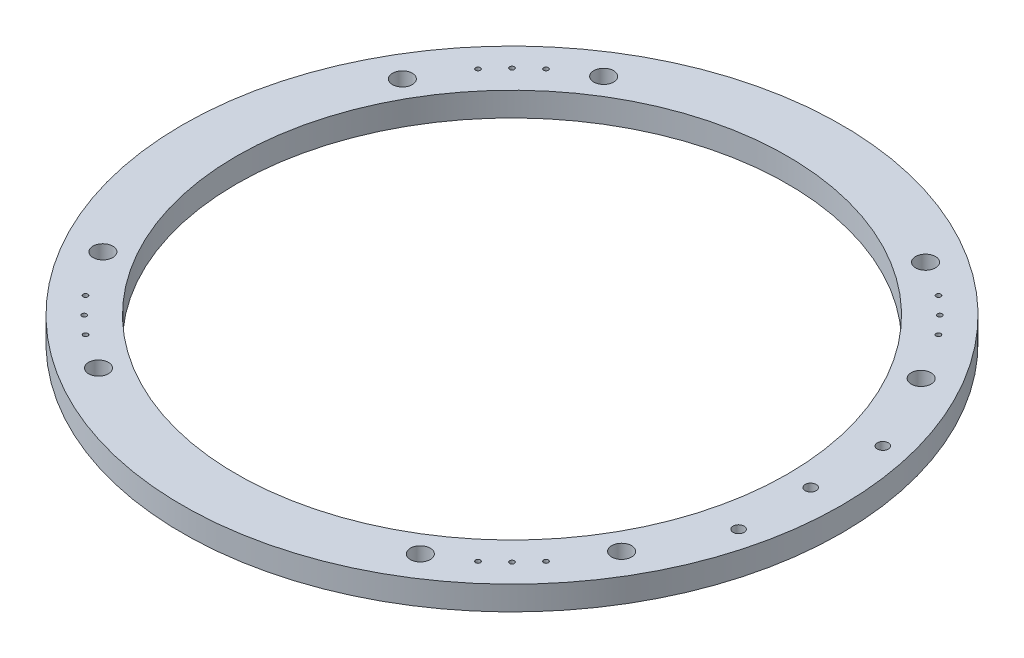
SolidWorks part; units mm, degrees
material "Oak"
ref_plane "Front Plane" through (0, 0, 0) normal (0, 0, 1) x (1, 0, 0)
ref_plane "Top Plane" through (0, 0, 0) normal (0, 1, 0) x (1, 0, 0)
ref_plane "Right Plane" through (0, 0, 0) normal (1, 0, 0) x (0, 0, -1)
sketch "Sketch1" plane through (0, 0, 0) normal (0, 0, 1) x (1, 0, 0)
  line L0 (0, 1125.8152) -> (0, -48874.1848) construction
  line L1 (145.5262, 1052.195) -> (152.4, 1052.195)
  line L9 (145.5262, 1064.895) -> (174.1012, 1064.895)
  line L10 (145.5262, 1064.895) -> (145.5262, 1052.195)
  line L11 (145.5262, 1052.195) -> (174.1012, 1052.195)
  line L12 (174.1012, 1064.895) -> (174.1012, 1052.195)
revolve "Revolve1" add sketch "Sketch1" angle 360 about L0 region at (159.8137, 1058.545, 0)
hole_wizard "Tap Drill for M3x0.5 Tap1" positions "Sketch9" profile "Sketch10" hole size "M3x0.5" standard "ANSI Metric" end condition through all
sketch "Sketch9" plane through (0, 1052.195, 0) normal (0, -1, 0) x (-1, 0, 0)
  line L0 (0, 0) -> (113.0054, 113.0054) construction
  line L3 (0, 0) -> (103.6677, 121.6282) construction
  arc A0 (103.6677, 121.6282) -> (121.6282, 103.6677) centre (0, 0) cw
  circle A1 centre (0, 0) radius 159.8137 construction
  point P0 (103.6677, 121.6282)
  point P2 (121.6282, 103.6677)
  point P15 (113.0054, 113.0054)
sketch "Sketch10" plane through (-103.6677, 1052.195, -121.6282) normal (1, 0, 0) x (0, 0, -1)
  line L0 (0, 0) -> (0, 12.7)
  line L1 (0, 12.7) -> (1.25, 12.7)
  line L2 (1.25, 12.7) -> (1.25, 0)
  line L5 (1.25, 0) -> (0, 0)
  line L11 (0, -6.35) -> (0, 107.95) construction
  dimension "Thru Hole Dia." = 2.5
  dimension "Thru Hole Depth" = 12.7
pattern_circular "CirPattern1" count 4 over 360 about axis through (0, 1125.8152, 0) along (0, 1, 0) of "Tap Drill for M3x0.5 Tap1"
ref_plane "Plane1" through (0, 1058.545, 0) normal (0, 1, 0) x (1, 0, 0)
hole_wizard "M5 Clearance Hole1" positions "Sketch14" profile "Sketch15" hole size "M5" standard "ANSI Metric" end condition through all
sketch "Sketch14" plane through (0, 1064.895, 0) normal (0, 1, 0) x (1, 0, 0)
  line L0 (157.7975, -38.1) -> (157.7975, 38.1) construction
  point P9 (157.7975, -38.1)
  point P12 (157.7975, 0)
  point P14 (157.7975, 38.1)
sketch "Sketch15" plane through (157.7975, 1064.895, 38.1) normal (1, 0, 0) x (0, 0, 1)
  line L0 (0, 0) -> (0, 12.7)
  line L1 (0, 12.7) -> (2.9, 12.7)
  line L2 (2.9, 12.7) -> (2.9, 0)
  line L5 (2.9, 0) -> (0, 0)
  line L11 (0, -6.35) -> (0, 107.95) construction
  dimension "Thru Hole Dia." = 5.8
  dimension "Thru Hole Depth" = 12.7
hole_wizard "Z (0.413) Diameter Hole1" positions "Sketch16" profile "Sketch17" hole size "Z" standard "ANSI Inch" end condition through all
sketch "Sketch16" plane through (0, 1064.895, 0) normal (0, 1, 0) x (1, 0, 0)
  line L0 (-137.0279, -79.1131) -> (137.0279, 79.1131) construction
  line L4 (137.0279, -79.1131) -> (-137.0279, 79.1131) construction
  line L6 (0, 0) -> (0, 158.2262) construction
  line L8 (-85.0149, -133.4467) -> (85.0149, 133.4467) construction
  line L11 (-85.0149, 133.4467) -> (85.0149, -133.4467) construction
  circle A0 centre (0, 0) radius 158.2262 construction
  circle A1 centre (0, 0) radius 145.5262 construction
  point P0 (-137.0279, -79.1131)
  point P2 (137.0279, -79.1131)
  point P4 (137.0279, 79.1131)
  point P6 (-137.0279, 79.1131)
  point P37 (-85.0149, 133.4467)
  point P39 (85.0149, 133.4467)
  point P41 (85.0149, -133.4467)
  point P43 (-85.0149, -133.4467)
  dimension "D2" = 12.7
  dimension "D1" = 120
  dimension "D3" = 65
sketch "Sketch17" plane through (-137.0279, 1064.895, 79.1131) normal (1, 0, 0) x (0, 0, 1)
  line L0 (0, 0) -> (0, 12.7)
  line L1 (0, 12.7) -> (5.2451, 12.7)
  line L2 (5.2451, 12.7) -> (5.2451, 0)
  line L5 (5.2451, 0) -> (0, 0)
  line L11 (0, -6.35) -> (0, 107.95) construction
  dimension "Thru Hole Dia." = 10.4902
  dimension "Thru Hole Depth" = 12.7
sketch "Sketch18" plane through (0, 1064.895, 0) normal (0, 1, 0) x (1, 0, 0)
  circle A5 centre (-103.6677, 121.6282) radius 1.5875
  circle A6 centre (-113.0054, 113.0054) radius 1.5875
  circle A7 centre (-121.6282, 103.6677) radius 1.5875
  circle A10 centre (103.6677, 121.6282) radius 1.5875
  circle A11 centre (113.0054, 113.0054) radius 1.5875
  circle A12 centre (121.6282, 103.6677) radius 1.5875
  circle A14 centre (-121.6282, -103.6677) radius 1.5875
  circle A37 centre (-113.0054, -113.0054) radius 1.5875
  circle A38 centre (-103.6677, -121.6282) radius 1.5875
  circle A39 centre (103.6677, -121.6282) radius 1.5875
  circle A40 centre (113.0054, -113.0054) radius 1.5875
  circle A41 centre (121.6282, -103.6677) radius 1.5875
  circle A53 centre (103.6677, 121.6282) radius 1.25
  circle A54 centre (103.6677, 121.6282) radius 1.25
  circle A55 centre (113.0054, 113.0054) radius 1.25
  circle A56 centre (113.0054, 113.0054) radius 1.25
  circle A57 centre (103.6677, -121.6282) radius 1.25
  circle A58 centre (103.6677, -121.6282) radius 1.25
  circle A59 centre (-121.6282, -103.6677) radius 1.25
  circle A60 centre (-121.6282, -103.6677) radius 1.25
  circle A61 centre (-103.6677, -121.6282) radius 1.25
  circle A62 centre (-103.6677, -121.6282) radius 1.25
  circle A63 centre (-113.0054, -113.0054) radius 1.25
  circle A64 centre (-113.0054, -113.0054) radius 1.25
  circle A65 centre (-103.6677, 121.6282) radius 1.25
  circle A66 centre (-103.6677, 121.6282) radius 1.25
  circle A67 centre (-121.6282, 103.6677) radius 1.25
  circle A68 centre (-121.6282, 103.6677) radius 1.25
  circle A69 centre (-113.0054, 113.0054) radius 1.25
  circle A70 centre (-113.0054, 113.0054) radius 1.25
  circle A73 centre (113.0054, -113.0054) radius 1.25
  circle A74 centre (113.0054, -113.0054) radius 1.25
  circle A75 centre (121.6282, -103.6677) radius 1.25
  circle A76 centre (121.6282, -103.6677) radius 1.25
  circle A77 centre (121.6282, 103.6677) radius 1.25
  circle A78 centre (121.6282, 103.6677) radius 1.25
  dimension "D13" = 3.175
  dimension "D14" = 0
  dimension "D15" = 0
  dimension "D16" = 0
  dimension "D17" = 0
  dimension "D18" = 0
  dimension "D19" = 0
  dimension "D20" = 0
  dimension "D21" = 0
  dimension "D22" = 0
  dimension "D24" = 0
  dimension "D25" = 0
  dimension "D26" = 0
extrude "Boss-Extrude1" [suppressed] add sketch "Sketch18" against normal up to surface (12.7 mm away) up to face at (-137.0279, 1052.195, 84.3582)
